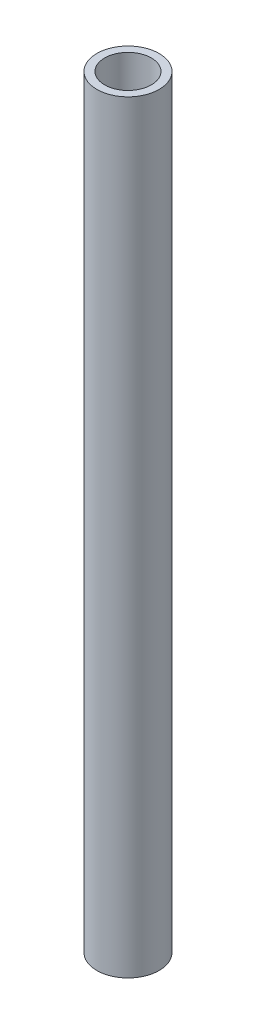
SolidWorks part; units mm, degrees
ref_plane "Front Plane" through (0, 0, 0) normal (0, 0, 1) x (1, 0, 0)
ref_plane "Top Plane" through (0, 0, 0) normal (0, 1, 0) x (1, 0, 0)
ref_plane "Right Plane" through (0, 0, 0) normal (1, 0, 0) x (0, 0, -1)
sketch "Sketch1" plane through (0, 0, 0) normal (0, 1, 0) x (1, 0, 0)
  circle A0 centre (-391.1817, 212.7433) radius 12.7
  circle A1 centre (-391.1817, 212.7433) radius 9.525
  dimension "D1" = 19.05
  dimension "D2" = 25.4
extrude "Boss-Extrude2" add sketch "Sketch1" along normal blind 311.15
